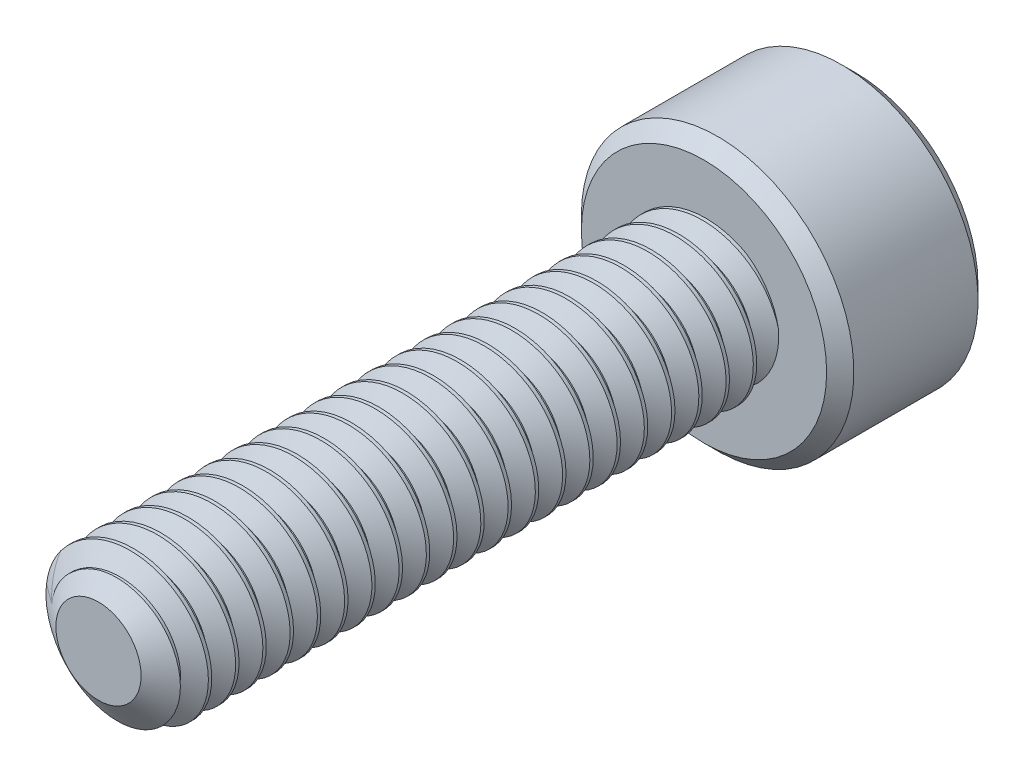
SolidWorks part; units mm, degrees
other "DetailItem1"
material "AISI Type 316L stainless steel"
ref_plane "Front Plane" through (0, 0, 0) normal (0, 0, 1) x (1, 0, 0)
ref_plane "Top Plane" through (0, 0, 0) normal (0, 1, 0) x (1, 0, 0)
ref_plane "Right Plane" through (0, 0, 0) normal (1, 0, 0) x (0, 0, -1)
sketch "Sketch1" plane through (0, 0, 0) normal (0, 0, 1) x (1, 0, 0)
  circle A0 centre (0, 0) radius 1.25
  dimension "OD" = 2.5
extrude "Extrude1" add sketch "Sketch1" against normal blind 10
sketch "Sketch2" plane through (0, 0, 0) normal (0, 0, 1) x (1, 0, 0)
  circle A0 centre (0, 0) radius 1.25 construction
  circle A1 centre (0, 0) radius 1.25
curve "Helix/Spiral1" pitch 0.45 height 10.45 turns 23.2222 parameters "pitch"=0.45
sketch "Sketch3" plane through (0, 0, 0) normal (1, 0, 0) x (0, 0, -1)
  line L0 (-0.3938, 1.25) -> (-0.225, 0.9577)
  line L1 (-0.225, 0.9577) -> (-0.1688, 0.9577)
  line L2 (-0.1688, 0.9577) -> (0, 1.25)
  line L3 (-0.3938, 1.25) -> (0, 1.25)
  line L4 (-0.1969, 1.25) -> (-0.1969, 0.9577) construction
  line L5 (-0.3094, 1.1039) -> (-0.0844, 1.1039) construction
  line L6 (0, 1.25) -> (0, -1.25) construction
  dimension "D1" = 0.0563
  dimension "D2" = 0.225
  dimension "D3" = 60
sweep "Cut-Sweep1" cut profiles "Sketch3" path "Helix/Spiral1" align with end faces yes
sketch "Sketch4" plane through (0, 0, 0) normal (1, 0, 0) x (0, 0, -1)
  line L0 (0.3825, 1.25) -> (0, 0.7037)
  line L1 (0, 0.7037) -> (0, 1.25)
  line L2 (0.3825, 1.25) -> (0, 1.25)
  line L3 (-0.3938, 1.25) -> (0, 1.25) construction
  line L4 (0, 0) -> (7.0209, 0) construction
  dimension "D1" = 55
  dimension "D2" = 0.254
revolve "Cut-Revolve1" cut sketch "Sketch4" angle 360 about L4
sketch "Sketch6" plane through (0, 0, -10) normal (0, 0, -1) x (-1, 0, 0)
  circle A0 centre (0, 0) radius 2.25
  dimension "head dia" = 4.5
extrude "Extrude2" add sketch "Sketch6" along normal blind 2.5
sketch "Sketch7" plane through (0, 0, -12.5) normal (0, 0, -1) x (-1, 0, 0)
  line L1 (0, 1.1547) -> (-1, 0.5774)
  line L2 (-1, 0.5774) -> (-1, -0.5774)
  line L3 (-1, -0.5774) -> (0, -1.1547)
  line L4 (0, -1.1547) -> (1, -0.5774)
  line L5 (1, -0.5774) -> (1, 0.5774)
  line L6 (1, 0.5774) -> (0, 1.1547)
  circle A0 centre (0, 0) radius 1 construction
  dimension "hex dia" = 2
extrude "Cut-Extrude1" cut sketch "Sketch7" against normal blind 1.5
sketch "Sketch8" plane through (0, 0, -12.5) normal (0, 0, -1) x (-1, 0, 0)
  circle A0 centre (0, 0) radius 1.1547
extrude "Cut-Extrude2" cut sketch "Sketch8" against normal through all draft 45
chamfer "Chamfer1" distance 0.225 angle 45 2 edges at (-2.25, 0, -12.5) (-2.25, 0, -10)
sketch "Sketch10" plane through (0, 0, -10) normal (0, 0, 1) x (1, 0, 0)
  circle A1 centre (0, 0) radius 1.25
  circle A2 centre (0, 0) radius 1.25
  dimension "D1" = 0
ref_plane "Plane1" through (0, 0, 0) normal (0, 0, 1) x (1, 0, 0)
extrude "partial thread" [suppressed] add sketch "Sketch10" along normal up to surface (36 mm away) separate body
chamfer "Chamfer2" [suppressed] distance 0.05 angle 45
combine bodies "Combine1" [suppressed] operation type add bodies to combine 107 108
sketch "Sketch9" plane through (0, 0, 0) normal (1, 0, 0) x (0, 0, -1)
  line L0 (0, 1.25) -> (0, -1.25) construction
  line L1 (1.125, 1.25) -> (1.125, -1.25) construction
  dimension "D1" = 1.125
equation "\"D3@Helix/Spiral1\" = \"screw length@Extrude1\"+\"pitch@Helix/Spiral1\""
equation "\"D1@Sketch3\" = \"pitch@Helix/Spiral1\"*.125"
equation "\"D2@Sketch3\" = \"pitch@Helix/Spiral1\"*.5"
equation "\"D1@Cut-Extrude1\" = \"hex dia@Sketch7\"*.75"
equation "\"D1@Chamfer1\" = \"head dia@Sketch6\"*.05"
equation "\"D1@Sketch9\" = \"pitch@Helix/Spiral1\"*2.5"
equation "\"D1@Chamfer2\"=\"OD@Sketch1\"*.02"
